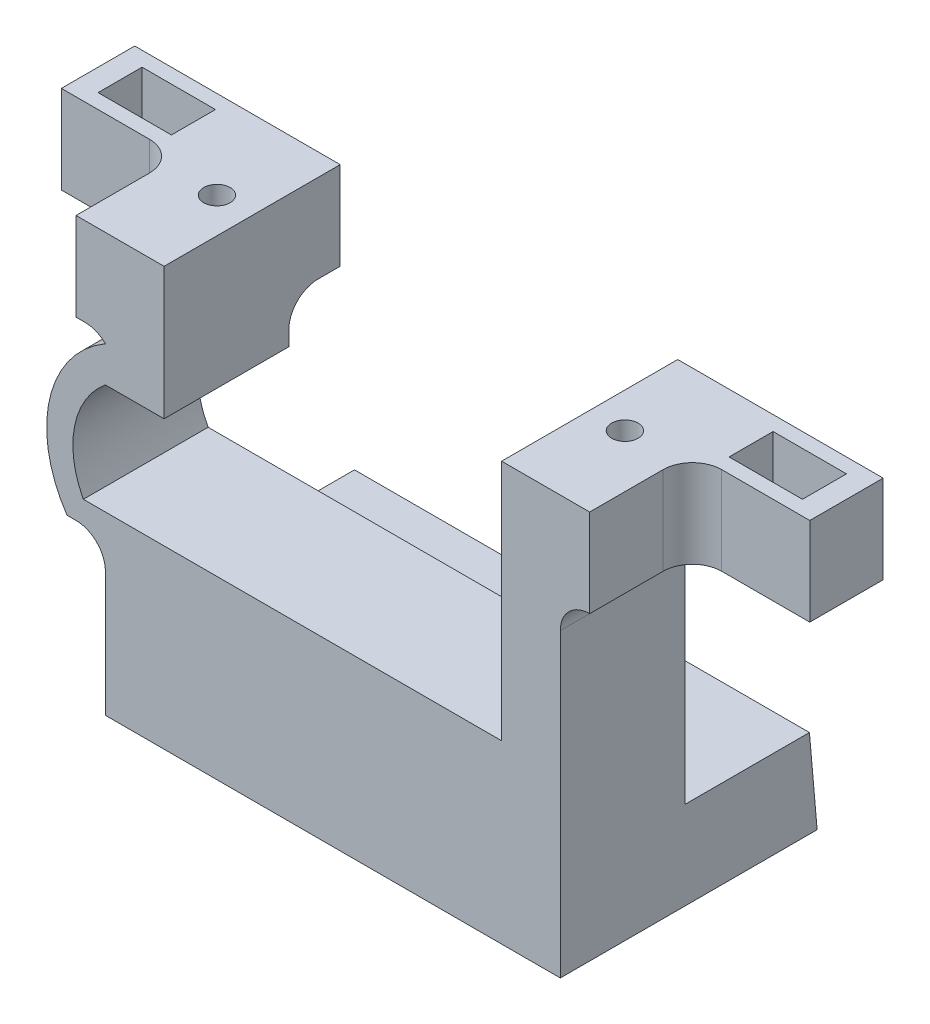
SolidWorks part; units mm, degrees
ref_plane "Front Plane" through (0, 0, 0) normal (0, 0, 1) x (1, 0, 0)
ref_plane "Top Plane" through (0, 0, 0) normal (0, 1, 0) x (1, 0, 0)
ref_plane "Right Plane" through (0, 0, 0) normal (1, 0, 0) x (0, 0, -1)
sketch "Sketch1" plane through (0, 0, 0) normal (0, 1, 0) x (1, 0, 0)
  line L0 (-11.5, 0) -> (11.5, 0) construction
  line L1 (-17.5, 6) -> (-11.5, 6)
  line L2 (-17.5, 6) -> (-17.5, -6)
  line L3 (-17.5, -6) -> (-11.5, -6)
  line L4 (-11.5, 6) -> (-11.5, -6)
  line L5 (11.5, 6) -> (17.5, 6)
  line L6 (11.5, 6) -> (11.5, -6)
  line L7 (11.5, -6) -> (17.5, -6)
  line L8 (17.5, 6) -> (17.5, -6)
  circle A0 centre (-13.9, 0) radius 0.9
  circle A1 centre (13.9, 0) radius 0.9
  dimension "D4" = 27.8
  dimension "D5" = 1.8
  dimension "D6" = 2.4
  dimension "D1" = 12
  dimension "D2" = 23
  dimension "D3" = 6
extrude "Servo Mounting Base" add sketch "Sketch1" along normal blind 6
sketch "Sketch2" plane through (0, 0, 0) normal (0, 0, 1) x (1, 0, 0)
  line L0 (-15.5, 0) -> (-15.5, -22.5)
  line L1 (-17.5, 0) -> (-11.5, 0) construction
  line L2 (-15.5, -22.5) -> (15.5, -22.5)
  line L3 (-15.5, 0) -> (-11.5, 0)
  line L4 (-11.5, 0) -> (-11.5, -10.5)
  line L5 (-11.5, -10.5) -> (11.5, -10.5)
  line L6 (-17.5, 6) -> (-11.5, 6) construction
  line L7 (0, 0) -> (0, -22.5) construction
  line L8 (15.5, 0) -> (11.5, 0)
  line L9 (11.5, 0) -> (11.5, -10.5)
  line L10 (15.5, 0) -> (15.5, -22.5)
  point P18 (0, -10.5)
  dimension "D1" = 16.5
  dimension "D2" = 12
  dimension "D3" = 4
extrude "Servo Enclosing Frame" add sketch "Sketch2" along normal mid plane 5
sketch "Sketch6" plane through (0, 0, 0) normal (0, 0, 1) x (1, 0, 0)
  line L0 (-11.5, -10.5) -> (-11.5, 0) construction
  line L2 (-11.5, -3) -> (-11.5, -12)
  line L3 (11.5, -10.5) -> (-11.5, -10.5) construction
  line L4 (-11.5, -3) -> (-15.5, -3)
  line L5 (-15.5, 0) -> (-15.5, -22.5) construction
  line L6 (-15.5, -3) -> (-15.5, -12)
  line L7 (-15.5, -12) -> (-11.5, -12)
  dimension "D1" = 7.5
  dimension "D2" = 1.5
extrude "Wire Slot" cut sketch "Sketch6" against normal through all both and the other way through all
sketch "Sketch7" plane through (0, 0, 0) normal (0, 0, 1) x (1, 0, 0)
  line L0 (-15.5, 0) -> (-15.5, -3) construction
  line L3 (-11.5, -10.5) -> (-11.5, -12) construction
  line L4 (-11.5, -3) -> (-11.5, -10.5) construction
  line L5 (-11.5, -12) -> (-18.1144, -12)
  line L6 (-11.5, -10.5) -> (-17, -10.5)
  line L7 (-15.5, -0.5718) -> (-15.5, -3)
  line L8 (-15.5, 0) -> (-15.5, -3) construction
  line L9 (-15.5, -12) -> (-15.5, -22.5) construction
  line L10 (-15.5, -3) -> (-11.5, -3) construction
  line L11 (-11.5, -12) -> (-15.5, -12) construction
  line L12 (-11.5, -12) -> (-11.5, -10.5)
  arc A0 (-18.1144, -12) -> (-15.5, -0.5718) centre (-11.5, -7.5) cw
  arc A3 (-15.5, -3) -> (-17, -10.5) centre (-11.7165, -7.6567) ccw
  dimension "D1" = 8
  dimension "D2" = 6
  dimension "D3" = 4.5
  dimension "D4" = 1.5
extrude "Wire Compensation" add sketch "Sketch7" along normal mid plane 5
sketch "Sketch9" plane through (-15.5, 0, 0) normal (-1, 0, 0) x (0, 0, 1)
  line L0 (-2.5, -22.5) -> (-11.5, -22.5)
  line L1 (-11.5, -22.5) -> (-10.9751, -16.5)
  line L2 (-10.9751, -16.5) -> (-2.5, -16.5)
  line L4 (-2.5, -16.5) -> (-2.5, -22.5)
  dimension "D1" = 85
  dimension "D2" = 9
  dimension "D3" = 6
extrude "Clamp Extension" add sketch "Sketch9" against normal up to surface (31 mm away) up to face at (15.5, -11.25, 0)
sketch "Sketch12" plane through (0, 0.8276, -9.4591) normal (0, 0.0872, -0.9962) x (-1, 0, 0)
  line L0 (0, -16.4167) -> (0, -23.4167)
  line L2 (-15.5, -23.4167) -> (15.5, -23.4167) construction
  line L3 (0, -23.4167) -> (-1.9, -23.4167)
  line L4 (-1.9, -23.4167) -> (-1.9, -16.4167)
  line L5 (-1.9, -16.4167) -> (0, -16.4167)
  dimension "D1" = 1.9
  dimension "D2" = 7
revolve "Wire Groove" cut sketch "Sketch12" angle 360 about L0
sketch "Sketch13" plane through (0, 0.8276, -9.4591) normal (0, 0.0872, -0.9962) x (-1, 0, 0)
  line L0 (-15.5, -20.4052) -> (15.5, -20.4052) construction
  line L1 (-15.5, -23.4167) -> (-15.5, -17.3938) construction
  line L2 (15.5, -17.3938) -> (15.5, -23.4167) construction
  line L3 (0, 0) -> (0, -23.5829) construction
  circle A0 centre (-8.5, -20.4052) radius 1.375
  circle A1 centre (8.5, -20.4052) radius 1.375
  ellipse E0 centre (0, -23.4167) end of major axis (-1.9, -23.4167) minor radius 0.1662 (-1.9, -23.4167) -> (1.9, -23.4167) ccw construction
  dimension "D1" = 2.75
  dimension "D2" = 7
extrude "Clamp Screw Holes" cut sketch "Sketch13" against normal blind 6
sketch "Sketch15" plane through (0, 6, 0) normal (0, 1, 0) x (1, 0, 0)
  line L0 (-21.5, 6) -> (-21.5, 1) construction
  line L1 (-17.5, 6) -> (-25.5, 6)
  line L2 (-17.5, 6) -> (-17.5, 1)
  line L3 (-17.5, 1) -> (-25.5, 1)
  line L4 (-25.5, 6) -> (-25.5, 1)
  line L5 (0, 0) -> (0, 9.0678) construction
  line L6 (-24, 5) -> (-19, 5)
  line L7 (-24, 5) -> (-24, 2)
  line L8 (-24, 2) -> (-19, 2)
  line L9 (-19, 5) -> (-19, 2)
  line L10 (-24, 5) -> (-19, 2) construction
  line L11 (-24, 2) -> (-19, 5) construction
  line L12 (17.5, 1) -> (25.5, 1)
  line L13 (25.5, 6) -> (25.5, 1)
  line L14 (17.5, 6) -> (25.5, 6)
  line L15 (17.5, 6) -> (17.5, 1)
  line L16 (24, 2) -> (19, 2)
  line L17 (19, 5) -> (19, 2)
  line L18 (24, 5) -> (19, 5)
  line L19 (24, 5) -> (24, 2)
  ellipse E0 centre (0, 10.9751) end of major axis (0, 9.0678) minor radius 1.9 (-1.9, 10.9751) -> (1.9, 10.9751) ccw construction
  point P7 (-21.5, 3.5)
  dimension "D1" = 8
  dimension "D2" = 5
  dimension "D3" = 5
  dimension "D4" = 3
extrude "Ziptie Flaps" add sketch "Sketch15" against normal blind 6
sketch "Sketch16" plane through (0, 0, 2.5) normal (0, 0, 1) x (1, 0, 0)
  line L0 (-15.5, 0) -> (-15.5, -0.5718)
  line L1 (-15.5, 0) -> (-11.5, 0)
  line L2 (-11.5, 0) -> (-11.5, -3)
  line L3 (-11.5, -3) -> (-11.5, 0) construction
  line L4 (-11.5, -3) -> (-15.5, -3)
  line L5 (-17, -10.5) -> (11.5, -10.5)
  line L6 (11.5, 0) -> (11.5, -10.5) construction
  line L7 (11.5, -10.5) -> (-17, -10.5) construction
  line L8 (11.5, -10.5) -> (11.5, 0)
  line L9 (11.5, 0) -> (15.5, 0)
  line L10 (11.5, 0) -> (17.5, 0) construction
  line L11 (15.5, 0) -> (15.5, -22.5)
  line L12 (15.5, -22.5) -> (-15.5, -22.5)
  line L13 (-15.5, -22.5) -> (-15.5, -12)
  line L14 (-15.5, -12) -> (-18.1144, -12)
  arc A0 (-18.1144, -12) -> (-15.5, -0.5718) centre (-11.5, -7.5) cw
  arc A1 (-17, -10.5) -> (-15.5, -3) centre (-11.7165, -7.6567) cw
  arc A2 (-15.5, -3) -> (-17, -10.5) centre (-11.7165, -7.6567) ccw construction
  arc A3 (-15.5, -0.5718) -> (-18.1144, -12) centre (-11.5, -7.5) ccw construction
extrude "Front Extension" add sketch "Sketch16" along normal up to surface (3.5 mm away) up to face at (-14.5, 3, 6)
fillet "2mm Fillets" radius 2 7 edges at (-15.5, -12, 1.75) (-15.5, 0, 1.75) (-13.5, 0, -2.5) (13.5, 0, -2.5) (15.5, 0, 1.75) (17.5, 3, -1) (-17.5, 3, -1)
